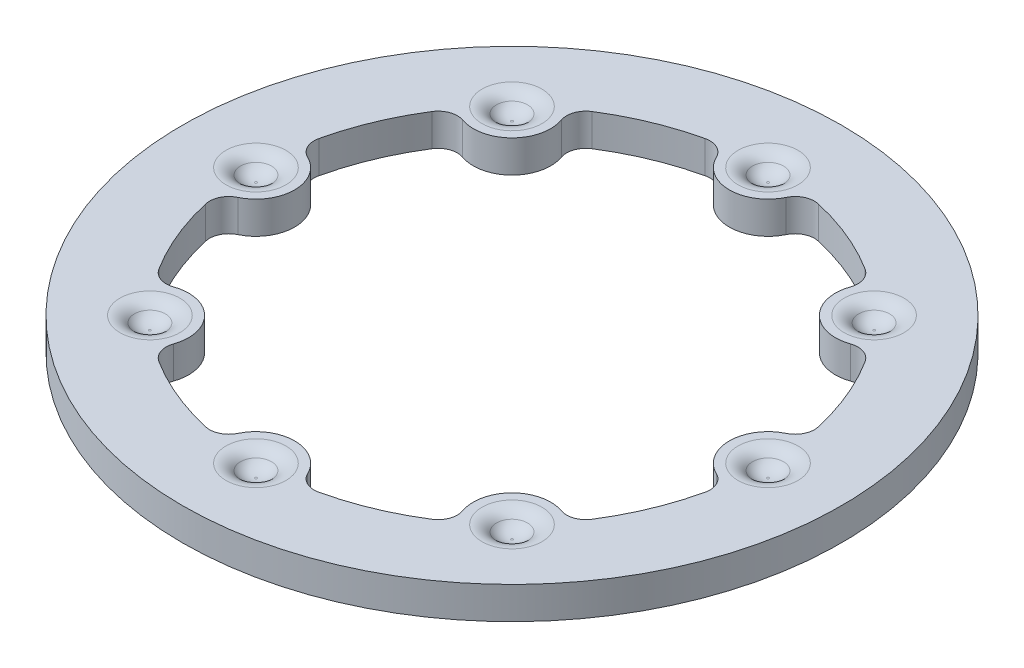
SolidWorks part; units mm, degrees
material "Brass"
ref_plane "Front Plane" through (0, 0, 0) normal (0, 0, 1) x (1, 0, 0)
ref_plane "Top Plane" through (0, 0, 0) normal (0, 1, 0) x (1, 0, 0)
ref_plane "Right Plane" through (0, 0, 0) normal (1, 0, 0) x (0, 0, -1)
sketch "Sketch1" plane through (0, 0, 0) normal (0, 1, 0) x (1, 0, 0)
  circle A0 centre (0, 0) radius 5.11
  circle A1 centre (0, 0) radius 3.97
  dimension "D1" = 10.22
  dimension "D2" = 7.94
extrude "Boss-Extrude1" add sketch "Sketch1" along normal blind 0.5
sketch "Sketch2" plane through (0, 0.5, 0) normal (0, 1, 0) x (1, 0, 0)
  circle A0 centre (0, 0) radius 3.97 construction
  circle A1 centre (0, 3.97) radius 0.6
  dimension "D1" = 1.2
extrude "Boss-Extrude2" add sketch "Sketch2" against normal up to surface (0.5 mm away) up to face at (0, 0, 5.11)
fillet "Fillet1" radius 0.3 2 edges at (-0.5983, 0.25, -3.9247) (0.5983, 0.25, -3.9247)
sketch "Sketch5" plane through (0, 0.5, 0) normal (0, 1, 0) x (1, 0, 0)
  circle A0 centre (0, 3.97) radius 0.3
  dimension "D1" = 0.6
extrude "Cut-Extrude1" cut sketch "Sketch5" against normal blind 0.2
pattern_circular "CirPattern4" count 8 over 360 about axis through (0, 0.5, 0) along (0, 1, 0) of "Boss-Extrude2", "Fillet1", "Cut-Extrude1"
fillet "Fillet2" radius 0.3 8 edges at (0, 0.3, -3.67) (2.5951, 0.3, -2.5951) (3.67, 0.3, 0) (2.5951, 0.3, 2.5951) (0, 0.3, 3.67) (-2.5951, 0.3, 2.5951) (-3.67, 0.3, 0) (-2.5951, 0.3, -2.5951)
fillet "Fillet3" radius 0.3 8 edges at (0, 0.5, -3.67) (2.5951, 0.5, -2.5951) (3.67, 0.5, 0) (2.5951, 0.5, 2.5951) (0, 0.5, 3.67) (-2.5951, 0.5, 2.5951) (-3.67, 0.5, 0) (-2.5951, 0.5, -2.5951)
equation "\"panjang\"= 120"
equation "\"lebar\"=40"
equation "\"tinggi\"=10"
